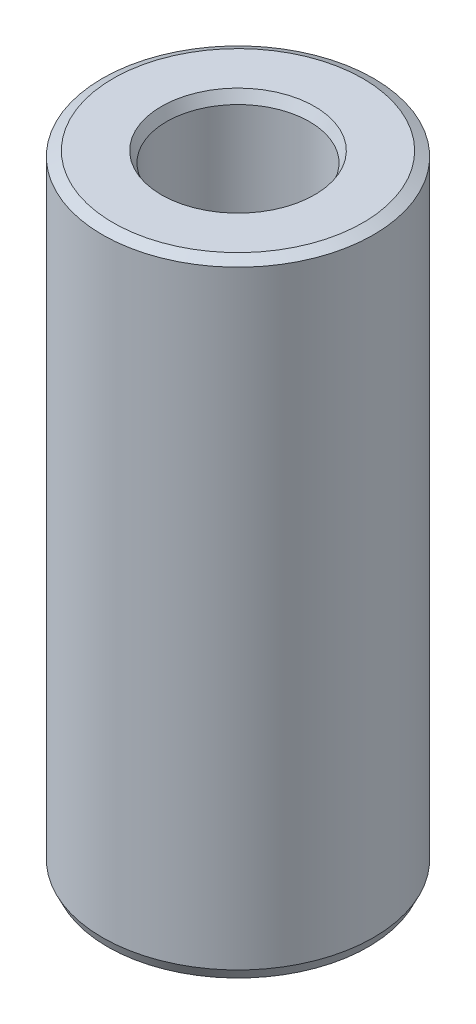
SolidWorks part; units mm, degrees
ref_plane "Front Plane" through (0, 0, 0) normal (0, 0, 1) x (1, 0, 0)
ref_plane "Top Plane" through (0, 0, 0) normal (0, 1, 0) x (1, 0, 0)
ref_plane "Right Plane" through (0, 0, 0) normal (1, 0, 0) x (0, 0, -1)
sketch "Sketch1" plane through (0, 0, 0) normal (0, 1, 0) x (1, 0, 0)
  circle A0 centre (0, 0) radius 50
  dimension "SLEEVE_OD" = 100
extrude "Boss-Extrude1" add sketch "Sketch1" along normal blind 230.3151
sketch "Sketch2" plane through (0, 0, 0) normal (0, 1, 0) x (1, 0, 0)
  circle A0 centre (0, 0) radius 26.3702
  dimension "BORE_D" = 52.7403
extrude "Cut-Extrude1" cut sketch "Sketch2" along normal through all
chamfer "Chamfer1" distance 1.8951 angle 64.165 4 edges at (0, 230.3151, 26.3702) (0, 0, 26.3702) (0, 0, 50) (0, 230.3151, 50) first distance on face at (0, 230.3151, 26.3702) first distance on face at (0, 0, 26.3702) first distance on face at (0, 230.3151, 50)
